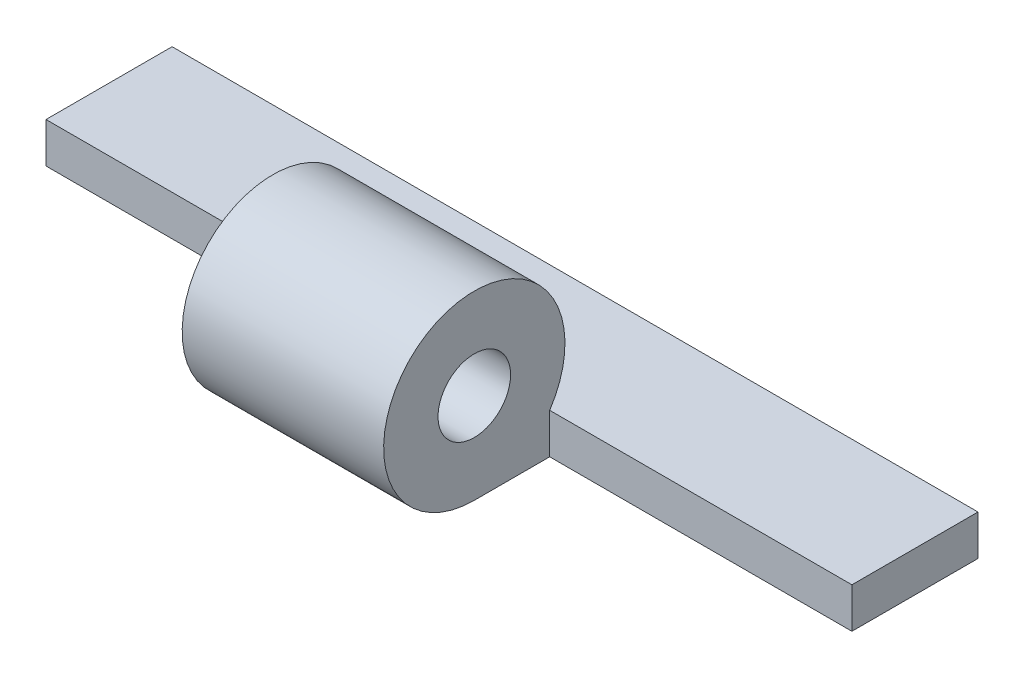
SolidWorks part; units mm, degrees
ref_plane "Ebene vorne" through (0, 0, 0) normal (0, 0, 1) x (1, 0, 0)
ref_plane "Ebene oben" through (0, 0, 0) normal (0, 1, 0) x (1, 0, 0)
ref_plane "Ebene rechts" through (0, 0, 0) normal (1, 0, 0) x (0, 0, -1)
sketch "Skizze2" plane through (0, 0, 0) normal (0, 1, 0) x (1, 0, 0)
  line L1 (-7.5, 2.5) -> (7.5, 2.5)
  line L2 (-7.5, 2.5) -> (-7.5, -2.5)
  line L3 (-7.5, -2.5) -> (7.5, -2.5)
  line L4 (7.5, 2.5) -> (7.5, -2.5)
  line L5 (-7.5, 2.5) -> (7.5, -2.5) construction
  line L6 (-7.5, -2.5) -> (7.5, 2.5) construction
  point P0 (0, 0)
  dimension "D1" = 15
  dimension "D2" = 5
extrude "Aufsatz-Linear austragen1" add sketch "Skizze2" along normal blind 1
sketch "Skizze3" plane through (7.5, 0, 0) normal (1, 0, 0) x (0, 0, -1)
  circle A0 centre (-2.5, 2.25) radius 2.25
  circle A1 centre (-2.5, 2.25) radius 0.9
  dimension "D1" = 1.8
  dimension "D2" = 4.5
extrude "Aufsatz-Linear austragen2" add sketch "Skizze3" against normal up to surface (15 mm away) up to face at (-7.5, 0.5, 0)
ref_plane "Tangential Ebene" through (0, 0, 0.25) normal (0, 0, -1) x (-1, 0, 0)
sketch "Skizze5" plane through (7.5, 0, 0) normal (1, 0, 0) x (0, 0, -1)
  line L0 (-0.6292, 1) -> (-0.6292, 0)
  line L1 (-0.6292, 0) -> (-2.5, 0)
  line L3 (2.5, 1) -> (-0.6292, 1)
  line L4 (-2.5, 0) -> (2.5, 0)
  line L5 (2.5, 0) -> (2.5, 1)
  line L6 (2.5, 1) -> (-0.6292, 1) construction
  line L7 (-2.5, 0) -> (2.5, 0) construction
  line L8 (2.5, 0) -> (2.5, 1) construction
  arc A1 (-0.6292, 1) -> (-2.5, 0) centre (-2.5, 2.25) ccw
  arc A2 (-0.6292, 1) -> (-2.5, 0) centre (-2.5, 2.25) ccw
  dimension "D1" = 0
extrude "Schnitt-Linear austragen1" cut sketch "Skizze5" against normal blind 5
pattern_linear "Lineares Muster1" count 2 spacing 10 along (-1, 0, 0) of "Schnitt-Linear austragen1"
ref_plane "Spiegelebene" through (0, 0, 0) normal (1, 0, 0) x (0, 0, -1)
sketch "Skizze7" plane through (7.5, 0, 0) normal (1, 0, 0) x (0, 0, -1)
  line L1 (2.5, 1) -> (-0.6292, 1)
  line L2 (2.5, 1) -> (2.5, 0)
  line L3 (2.5, 0) -> (-0.6292, 0)
  line L4 (-0.6292, 1) -> (-0.6292, 0)
extrude "Verbreiterung" add sketch "Skizze7" along normal blind 2.5
mirror "Spiegeln1" about plane through (0, 0, 0) normal (1, 0, 0) of "Verbreiterung"
ref_axis "Achse1" through (-2.5, 2.25, 2.5) along (1, 0, 0)
